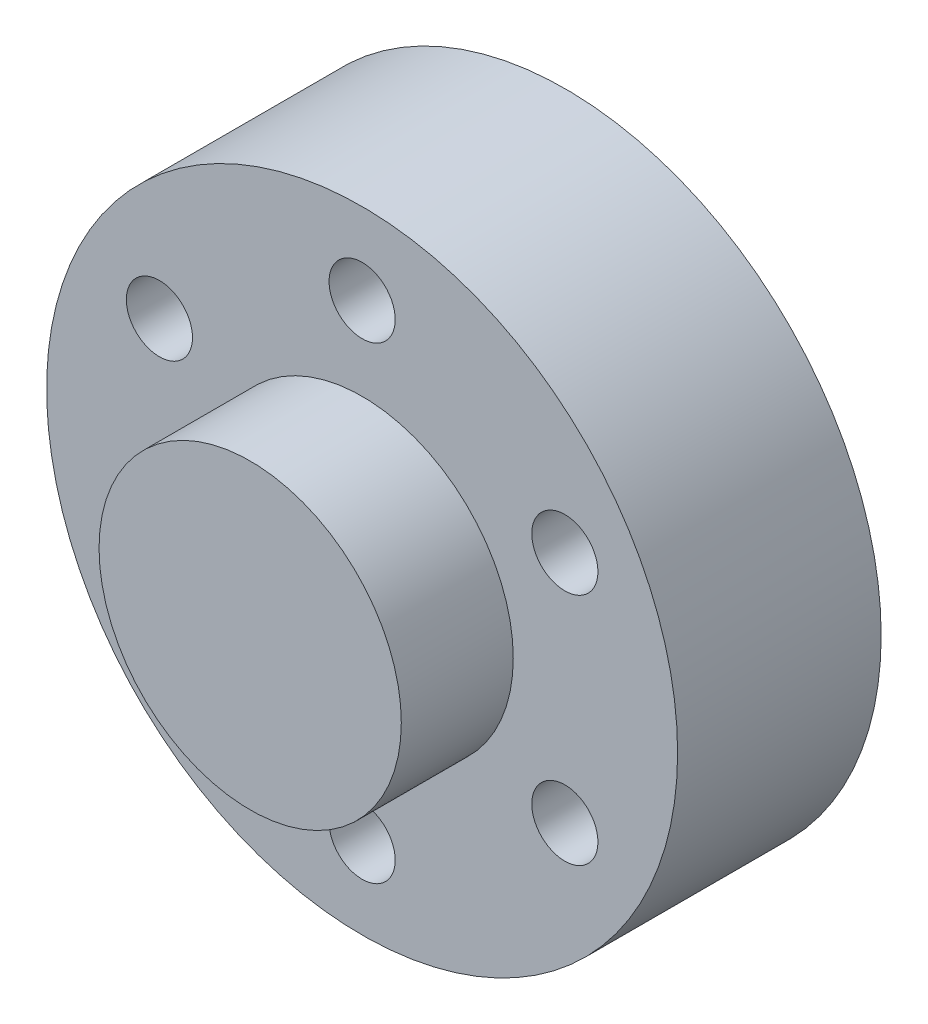
SolidWorks part; units mm, degrees
ref_plane "Front Plane" through (0, 0, 0) normal (0, 0, 1) x (1, 0, 0)
ref_plane "Top Plane" through (0, 0, 0) normal (0, 1, 0) x (1, 0, 0)
ref_plane "Right Plane" through (0, 0, 0) normal (1, 0, 0) x (0, 0, -1)
sketch "Sketch2" plane through (0, 0, 0) normal (0, 0, 1) x (1, 0, 0)
  line L0 (0, 20.3178) -> (0, -21.083) construction
  circle A0 centre (0, 0) radius 9.5
  circle A1 centre (0, 0) radius 11.5 construction
  circle A3 centre (0, 0) radius 15.5
  circle A4 centre (0, 11.5) radius 1.625
  circle A10 centre (9.9593, 5.75) radius 1.625
  circle A11 centre (9.9593, -5.75) radius 1.625
  circle A12 centre (0, -11.5) radius 1.625
  circle A13 centre (-9.9593, -5.75) radius 1.625
  circle A14 centre (-9.9593, 5.75) radius 1.625
  point P21 (1.7321, -1)
  point P22 (0.866, -0.5)
  point P23 (0, 0)
  dimension "D1" = 19
  dimension "D2" = 6
  dimension "D3" = 23
  dimension "D4" = 31
  dimension "D5" = 3.25
extrude "Boss-Extrude1" add sketch "Sketch2" along normal blind 10 contours A3 A14 A13 A12 A11 A10 A4 A0 | A0 region at (0, 0, 0) region at (-15.0616, 0, 0)
sketch "Sketch3" plane through (0, 0, 10) normal (0, 0, 1) x (1, 0, 0)
  circle A0 centre (0, 0) radius 7.425
  dimension "D1" = 14.85
extrude "Boss-Extrude2" add sketch "Sketch3" along normal blind 5.5
sketch "Sketch6" plane through (0, 0, 0) normal (0, 0, -1) x (-1, 0, 0)
  circle A0 centre (0, 0) radius 7.425
  dimension "D1" = 14.85
extrude "Boss-Extrude4" add sketch "Sketch6" along normal blind 5.5 contours A0
sketch "Sketch7" plane through (0, 0, -5.5) normal (0, 0, -1) x (-1, 0, 0)
  circle A0 centre (0, 0) radius 2
  dimension "D1" = 4
extrude "Boss-Extrude5" add sketch "Sketch7" along normal blind 1
fillet "Fillet2" radius 0.05 1 edges at (-2, 0, -6.5)
sketch "Sketch9" plane through (0, 0, -6.5) normal (0, 0, -1) x (-1, 0, 0)
  line L1 (-1.2247, 1.25) -> (1.2247, 1.25)
  arc A0 (-1.2247, 1.25) -> (1.2247, 1.25) centre (0, 0) ccw
  circle A1 centre (0, -0.25) radius 1.5 construction
  dimension "D1" = 3.5
  dimension "D2" = 3
extrude "Cut-Extrude1" cut sketch "Sketch9" against normal blind 11
sketch "Sketch10" plane through (0, 0, -5.5) normal (0, 0, -1) x (-1, 0, 0)
  line L0 (-7.425, 0) -> (7.425, 0) construction
  line L1 (0, 7.425) -> (0, -7.425) construction
  line L2 (0, 0) -> (4.5, 0) construction
  circle A0 centre (0, 0) radius 7.425 construction
  circle A1 centre (0, 0) radius 7.425 construction
  circle A2 centre (4.5, 0) radius 0.8
  circle A3 centre (-4.5, 0) radius 0.8
  dimension "D2" = 1.6
  dimension "D1" = 4.5
extrude "Cut-Extrude2" cut sketch "Sketch10" against normal blind 2.5
